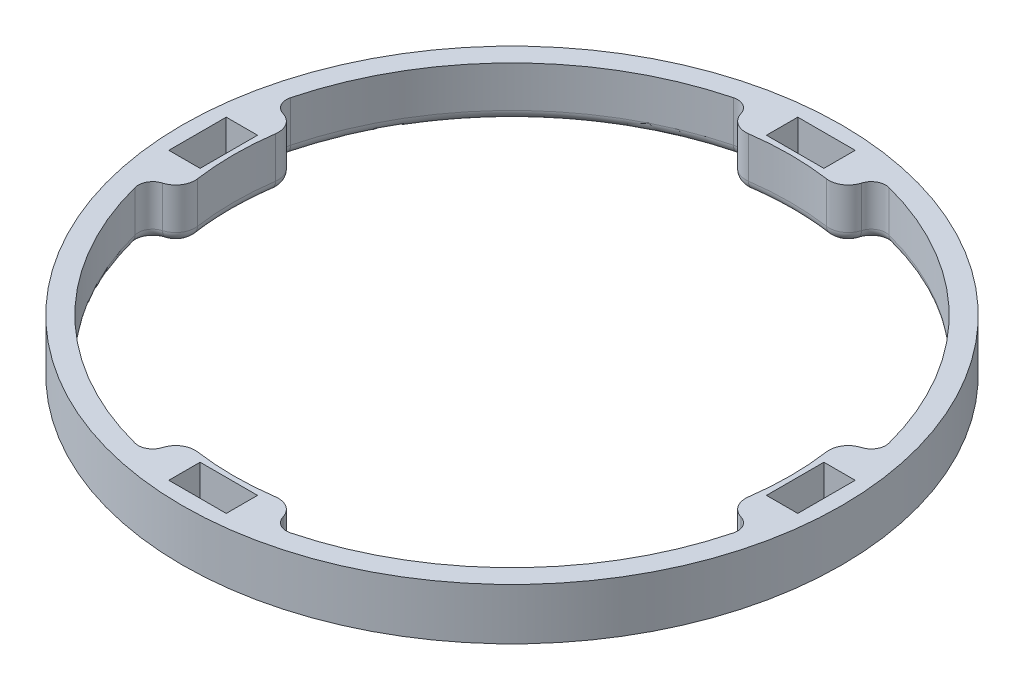
SolidWorks part; units mm, degrees
ref_plane "Front Plane" through (0, 0, 0) normal (0, 0, 1) x (1, 0, 0)
ref_plane "Top Plane" through (0, 0, 0) normal (0, 1, 0) x (1, 0, 0)
ref_plane "Right Plane" through (0, 0, 0) normal (1, 0, 0) x (0, 0, -1)
sketch "Sketch1" plane through (0, 0, 0) normal (0, 1, 0) x (1, 0, 0)
  circle A0 centre (0, 0) radius 32.035
  circle A1 centre (0, 0) radius 27.035
  dimension "D1" = 64.07
  dimension "D2" = 5
extrude "Boss-Extrude1" add sketch "Sketch1" along normal mid plane 5
sketch "Sketch2" plane through (0, 2.5, 0) normal (0, 1, 0) x (1, 0, 0)
  line L1 (-2.79, 30.555) -> (2.79, 30.555)
  line L2 (-2.79, 30.555) -> (-2.79, 27.515)
  line L3 (-2.79, 27.515) -> (2.79, 27.515)
  line L4 (2.79, 30.555) -> (2.79, 27.515)
  line L5 (-2.79, 30.555) -> (2.79, 27.515) construction
  line L6 (-2.79, 27.515) -> (2.79, 30.555) construction
  circle A0 centre (0, 0) radius 32.035 construction
  point P0 (0, 29.035)
  point P5 (0, 32.035)
  point P6 (0, 0)
  dimension "D1" = 3
  dimension "D2" = 3.04
  dimension "D3" = 5.58
extrude "Cut-Extrude1" cut sketch "Sketch2" against normal through all
pattern_circular "CirPattern1" count 4 over 360 about axis through (0, 2.5, 0) along (0, -1, 0) of "Cut-Extrude1" reverse direction yes
sketch "Sketch3" plane through (0, 2.5, 0) normal (0, 1, 0) x (1, 0, 0)
  line L0 (-27.515, 2.79) -> (-30.555, 2.79) construction
  line L1 (-2.79, 30.555) -> (-2.79, 27.515) construction
  arc A0 (-29.0698, 7.5531) -> (-7.5531, 29.0698) centre (0, 0) cw
  arc A1 (-26.768, 3.79) -> (-3.79, 26.768) centre (0, 0) cw
  circle A2 centre (0, 0) radius 27.035 construction
  arc A3 (-26.768, 3.79) -> (-28.1016, 5.8517) centre (-28.6226, 4.0526) ccw
  arc A4 (-28.1016, 5.8517) -> (-29.0698, 7.5531) centre (-27.7112, 7.2001) cw
  arc A5 (-3.79, 26.768) -> (-5.8517, 28.1016) centre (-4.0526, 28.6226) cw
  arc A6 (-5.8517, 28.1016) -> (-7.5531, 29.0698) centre (-7.2001, 27.7112) ccw
  circle A7 centre (0, 0) radius 32.035 construction
  point P14 (0, 0)
  point P15 (-26.5548, 5.073)
  point P16 (-28.1888, 6.5942)
  point P17 (-28.7951, 9.9624)
  point P18 (-27.6903, 7.5777)
  point P19 (-9.9614, 28.8105)
  point P20 (-7.0712, 27.5828)
  point P27 (0, 0)
  point P28 (-27.7376, 6.7376)
  point P29 (-5.6939, 27.9705)
  point P30 (-28.1016, 5.8517)
  dimension "D1" = 2
  dimension "D2" = 1
  dimension "D3" = 1
extrude "Cut-Extrude2" cut sketch "Sketch3" against normal through all
pattern_circular "CirPattern2" count 4 over 360 about axis through (0, 2.5, 0) along (0, -1, 0) of "Cut-Extrude2"
fillet "Fillet1" radius 1 24 edges at (-6.5058, -2.5, -28.9312) (-5.0699, -2.5, -27.0499) (0, -2.5, -27.035) (5.0699, -2.5, -27.0499) (6.5058, -2.5, -28.9312) (21.238, -2.5, -21.238) (28.9312, -2.5, -6.5058) (27.0499, -2.5, -5.0699) (27.035, -2.5, 0) (27.0499, -2.5, 5.0699) (28.9312, -2.5, 6.5058) (21.238, -2.5, 21.238) (6.5058, -2.5, 28.9312) (5.0699, -2.5, 27.0499) (0, -2.5, 27.035) (-5.0699, -2.5, 27.0499) (-6.5058, -2.5, 28.9312) (-21.238, -2.5, 21.238) (-28.9312, -2.5, 6.5058) (-27.0499, -2.5, 5.0699) (-27.035, -2.5, 0) (-27.0499, -2.5, -5.0699) (-28.9312, -2.5, -6.5058) (-21.238, -2.5, -21.238)
